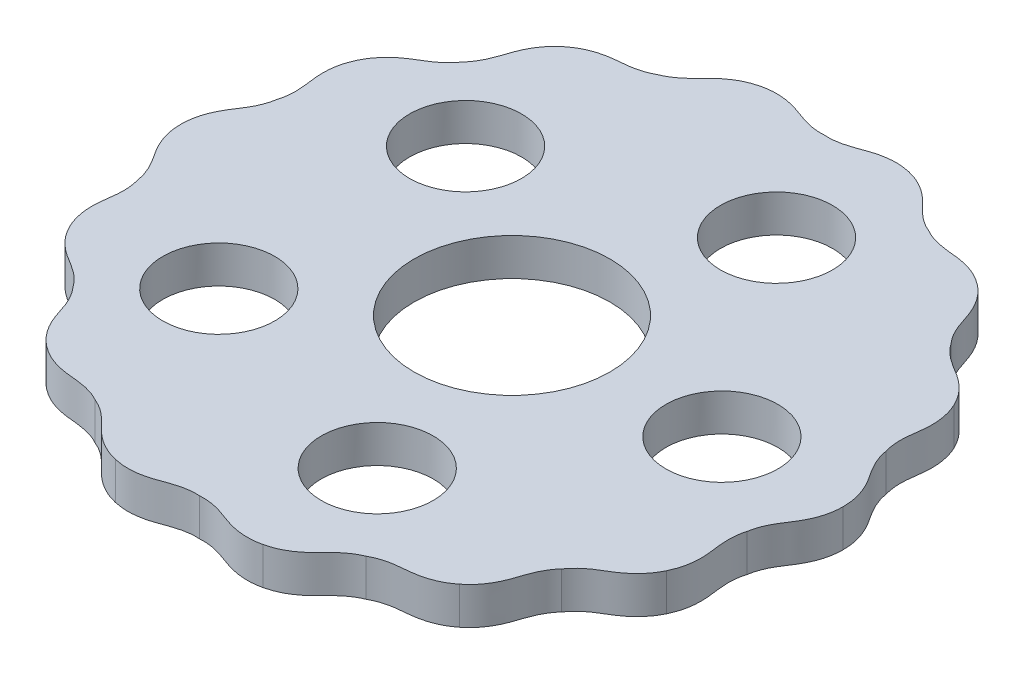
SolidWorks part; units mm, degrees
ref_plane "Front Plane" through (0, 0, 0) normal (0, 0, 1) x (1, 0, 0)
ref_plane "Top Plane" through (0, 0, 0) normal (0, 1, 0) x (1, 0, 0)
ref_plane "Right Plane" through (0, 0, 0) normal (1, 0, 0) x (0, 0, -1)
sketch "Sketch1" plane through (0, 0, 0) normal (0, 1, 0) x (1, 0, 0)
  line L0 (0, 0) -> (37.5, 0) construction
  line L1 (0, 0) -> (37.4807, 1.2019) construction
  line L2 (0, 0) -> (37.423, 2.4026) construction
  line L3 (0, 0) -> (37.3267, 3.6009) construction
  line L4 (0, 0) -> (37.1921, 4.7954) construction
  line L5 (0, 0) -> (37.0193, 5.985) construction
  line L6 (0, 0) -> (36.8085, 7.1684) construction
  line L7 (0, 0) -> (36.5598, 8.3445) construction
  line L8 (0, 0) -> (36.2736, 9.512) construction
  line L9 (0, 0) -> (35.95, 10.6698) construction
  line L10 (0, 0) -> (35.5896, 11.8166) construction
  line L11 (0, 0) -> (35.1926, 12.9512) construction
  line L12 (0, 0) -> (34.7594, 14.0725) construction
  line L13 (0, 0) -> (34.2905, 15.1794) construction
  line L14 (0, 0) -> (33.7863, 16.2706) construction
  line L15 (37.5, 0) -> (38.5, 0) construction
  line L16 (37.4807, 1.2019) -> (38.3521, 1.6927) construction
  line L17 (37.423, 2.4026) -> (37.9413, 3.2578) construction
  line L18 (37.3267, 3.6009) -> (37.3588, 4.6003) construction
  line L19 (37.1921, 4.7954) -> (36.7296, 5.682) construction
  line L20 (37.0193, 5.985) -> (36.1812, 6.5305) construction
  line L21 (36.8085, 7.1684) -> (35.8105, 7.2325) construction
  line L22 (36.5598, 8.3445) -> (35.5849, 8.122) construction
  line L23 (37, 0.0019) -> (37, 0)
  line L24 (33.3367, 16.052) -> (33.3358, 16.0537)
  line L25 (37, -0.0019) -> (37, 0)
  line L26 (33.3367, -16.052) -> (33.3358, -16.0537)
  line L27 (33.335, -16.0554) -> (33.3358, -16.0537)
  line L28 (23.0706, -28.9266) -> (23.0691, -28.9278)
  line L29 (23.0677, -28.9289) -> (23.0691, -28.9278)
  line L30 (8.2351, -36.0719) -> (8.2333, -36.0723)
  line L31 (8.2315, -36.0727) -> (8.2333, -36.0723)
  line L32 (-8.2315, -36.0727) -> (-8.2333, -36.0723)
  line L33 (-8.2351, -36.0719) -> (-8.2333, -36.0723)
  line L34 (-23.0677, -28.9289) -> (-23.0691, -28.9278)
  line L35 (-23.0706, -28.9266) -> (-23.0691, -28.9278)
  line L36 (-33.335, -16.0554) -> (-33.3358, -16.0537)
  line L37 (-33.3367, -16.052) -> (-33.3358, -16.0537)
  line L38 (-37, -0.0019) -> (-37, 0)
  line L39 (-37, 0.0019) -> (-37, 0)
  line L40 (-33.3367, 16.052) -> (-33.3358, 16.0537)
  line L41 (-33.335, 16.0554) -> (-33.3358, 16.0537)
  line L42 (-23.0706, 28.9266) -> (-23.0691, 28.9278)
  line L43 (-23.0677, 28.9289) -> (-23.0691, 28.9278)
  line L44 (-8.2351, 36.0719) -> (-8.2333, 36.0723)
  line L45 (-8.2315, 36.0727) -> (-8.2333, 36.0723)
  line L46 (8.2315, 36.0727) -> (8.2333, 36.0723)
  line L47 (8.2351, 36.0719) -> (8.2333, 36.0723)
  line L48 (23.0677, 28.9289) -> (23.0691, 28.9278)
  line L49 (23.0706, 28.9266) -> (23.0691, 28.9278)
  line L50 (33.335, 16.0554) -> (33.3358, 16.0537)
  line L51 (35.5, 0.0037) -> (35.5, 0)
  line L52 (31.986, 15.3995) -> (31.9844, 15.4029)
  line L53 (35.5, -0.0037) -> (35.5, 0)
  line L54 (31.986, -15.3995) -> (31.9844, -15.4029)
  line L55 (31.9828, -15.4062) -> (31.9844, -15.4029)
  line L56 (22.1368, -27.7527) -> (22.1339, -27.755)
  line L57 (22.131, -27.7573) -> (22.1339, -27.755)
  line L58 (7.9031, -34.6091) -> (7.8995, -34.6099)
  line L59 (7.8959, -34.6108) -> (7.8995, -34.6099)
  line L60 (-7.8959, -34.6108) -> (-7.8995, -34.6099)
  line L61 (-7.9031, -34.6091) -> (-7.8995, -34.6099)
  line L62 (-22.131, -27.7573) -> (-22.1339, -27.755)
  line L63 (-22.1368, -27.7527) -> (-22.1339, -27.755)
  line L64 (-31.9828, -15.4062) -> (-31.9844, -15.4029)
  line L65 (-31.986, -15.3995) -> (-31.9844, -15.4029)
  line L66 (-35.5, -0.0037) -> (-35.5, 0)
  line L67 (-35.5, 0.0037) -> (-35.5, 0)
  line L68 (-31.986, 15.3995) -> (-31.9844, 15.4029)
  line L69 (-31.9828, 15.4062) -> (-31.9844, 15.4029)
  line L70 (-22.1368, 27.7527) -> (-22.1339, 27.755)
  line L71 (-22.131, 27.7573) -> (-22.1339, 27.755)
  line L72 (-7.9031, 34.6091) -> (-7.8995, 34.6099)
  line L73 (-7.8959, 34.6108) -> (-7.8995, 34.6099)
  line L74 (7.8959, 34.6108) -> (7.8995, 34.6099)
  line L75 (7.9031, 34.6091) -> (7.8995, 34.6099)
  line L76 (22.131, 27.7573) -> (22.1339, 27.755)
  line L77 (22.1368, 27.7527) -> (22.1339, 27.755)
  line L78 (31.9828, 15.4062) -> (31.9844, 15.4029)
  circle A0 centre (0, 0) radius 35 construction
  circle A1 centre (37.5, 0) radius 2.5 construction
  circle A2 centre (0, 0) radius 37.5 construction
  spline S0 degree 3 poles (35.5849, 8.122) (35.6266, 7.5364) (36.0345, 6.7125) (36.7836, 5.6218) (37.4152, 4.5501) (38.2239, 2.702) (38.5014, 1.1074) (38.5, 0) knots 0 0 0 0 0.195516 0.310928 0.453873 0.621058 1 1 1 1
  spline S1 degree 3 poles (35.5849, 8.122) (35.3683, 8.6678) (35.3784, 9.5871) (35.5801, 10.8948) (35.6841, 12.1344) (35.611, 14.1503) (35.169, 15.7074) (34.6873, 16.7045) knots 0 0 0 0 0.195516 0.310928 0.453873 0.621058 1 1 1 1
  spline S2 degree 1 poles (34.1119, 7.7858) (33.3367, 16.052) knots 0 0 1 1 construction
  spline S3 degree 1 poles (34.1119, 7.7858) (37, 0.0019) knots 0 0 1 1 construction
  spline S4 degree 3 poles (33.3367, 16.052) (33.6005, 15.5058) (33.9037, 14.6401) (34.1146, 13.4372) (34.174, 12.5211) (34.1413, 11.5771) (34.0239, 10.6392) (33.8823, 9.6155) (33.9055, 8.625) (34.0243, 8.0514) (34.1119, 7.7858) knots 0.015853 0.015853 0.015853 0.015853 0.26189 0.384908 0.507927 0.630945 0.753963 0.876982 0.938491 1 1 1 1
  spline S5 degree 3 poles (34.1119, 7.7858) (34.1483, 7.5085) (34.2901, 6.9402) (34.6989, 6.0377) (35.2706, 5.1769) (35.7834, 4.3828) (36.2224, 3.5464) (36.5664, 2.6953) (36.8983, 1.52) (37.0008, 0.6085) (37, 0.0019) knots 0.015853 0.015853 0.015853 0.015853 0.077362 0.138872 0.26189 0.384908 0.507927 0.630945 0.753963 1 1 1 1
  spline S6 degree 3 poles (37, -0.0019) (37.0008, -0.6085) (36.8983, -1.52) (36.5664, -2.6953) (36.2224, -3.5464) (35.7834, -4.3828) (35.2706, -5.1769) (34.6989, -6.0377) (34.2901, -6.9402) (34.1483, -7.5085) (34.1119, -7.7858) knots 0.015853 0.015853 0.015853 0.015853 0.26189 0.384908 0.507927 0.630945 0.753963 0.876982 0.938491 1 1 1 1
  spline S7 degree 3 poles (34.1119, -7.7858) (34.0243, -8.0514) (33.9055, -8.625) (33.8823, -9.6155) (34.0239, -10.6392) (34.1413, -11.5771) (34.174, -12.5211) (34.1146, -13.4372) (33.9037, -14.6401) (33.6005, -15.5058) (33.3367, -16.052) knots 0.015853 0.015853 0.015853 0.015853 0.077362 0.138872 0.26189 0.384908 0.507927 0.630945 0.753963 1 1 1 1
  spline S8 degree 3 poles (33.335, -16.0554) (33.0725, -16.6022) (32.5847, -17.3791) (31.7758, -18.2939) (31.0965, -18.9115) (30.3381, -19.4746) (29.5316, -19.9675) (28.6429, -20.4951) (27.8831, -21.1308) (27.5087, -21.5813) (27.3556, -21.8154) knots 0.015853 0.015853 0.015853 0.015853 0.26189 0.384908 0.507927 0.630945 0.753963 0.876982 0.938491 1 1 1 1
  spline S9 degree 3 poles (27.3556, -21.8154) (27.1615, -22.0167) (26.8056, -22.4819) (26.3549, -23.3642) (26.0383, -24.348) (25.7371, -25.2439) (25.357, -26.1087) (24.906, -26.9083) (24.1941, -27.9005) (23.5453, -28.549) (23.0706, -28.9266) knots 0.015853 0.015853 0.015853 0.015853 0.077362 0.138872 0.26189 0.384908 0.507927 0.630945 0.753963 1 1 1 1
  spline S10 degree 3 poles (23.0677, -28.9289) (22.5939, -29.3077) (21.8173, -29.796) (20.6915, -30.2693) (19.8116, -30.531) (18.884, -30.7092) (17.9435, -30.8034) (16.9139, -30.8931) (15.9535, -31.1362) (15.4207, -31.3797) (15.1812, -31.5241) knots 0.015853 0.015853 0.015853 0.015853 0.26189 0.384908 0.507927 0.630945 0.753963 0.876982 0.938491 1 1 1 1
  spline S11 degree 3 poles (15.1812, -31.5241) (14.919, -31.6213) (14.3964, -31.886) (13.6076, -32.4854) (12.8955, -33.2344) (12.2354, -33.9109) (11.5177, -34.5251) (10.7645, -35.0499) (9.6926, -35.6349) (8.8266, -35.9377) (8.2351, -36.0719) knots 0.015853 0.015853 0.015853 0.015853 0.077362 0.138872 0.26189 0.384908 0.507927 0.630945 0.753963 1 1 1 1
  spline S12 degree 3 poles (8.2315, -36.0727) (7.6402, -36.2085) (6.7287, -36.3114) (5.5091, -36.2494) (4.6028, -36.1034) (3.6897, -35.8614) (2.8014, -35.5383) (1.8349, -35.1724) (0.8641, -34.9747) (0.2785, -34.9629) (0, -34.9891) knots 0.015853 0.015853 0.015853 0.015853 0.26189 0.384908 0.507927 0.630945 0.753963 0.876982 0.938491 1 1 1 1
  spline S13 degree 3 poles (0, -34.9891) (-0.2785, -34.9629) (-0.8641, -34.9747) (-1.8349, -35.1724) (-2.8014, -35.5383) (-3.6897, -35.8614) (-4.6028, -36.1034) (-5.5091, -36.2494) (-6.7287, -36.3114) (-7.6402, -36.2085) (-8.2315, -36.0727) knots 0.015853 0.015853 0.015853 0.015853 0.077362 0.138872 0.26189 0.384908 0.507927 0.630945 0.753963 1 1 1 1
  spline S14 degree 3 poles (-8.2351, -36.0719) (-8.8266, -35.9377) (-9.6926, -35.6349) (-10.7645, -35.0499) (-11.5177, -34.5251) (-12.2354, -33.9109) (-12.8955, -33.2344) (-13.6076, -32.4854) (-14.3964, -31.886) (-14.919, -31.6213) (-15.1812, -31.5241) knots 0.015853 0.015853 0.015853 0.015853 0.26189 0.384908 0.507927 0.630945 0.753963 0.876982 0.938491 1 1 1 1
  spline S15 degree 3 poles (-15.1812, -31.5241) (-15.4207, -31.3797) (-15.9535, -31.1362) (-16.9139, -30.8931) (-17.9435, -30.8034) (-18.884, -30.7092) (-19.8116, -30.531) (-20.6915, -30.2693) (-21.8173, -29.796) (-22.5939, -29.3077) (-23.0677, -28.9289) knots 0.015853 0.015853 0.015853 0.015853 0.077362 0.138872 0.26189 0.384908 0.507927 0.630945 0.753963 1 1 1 1
  spline S16 degree 3 poles (-23.0706, -28.9266) (-23.5453, -28.549) (-24.1941, -27.9005) (-24.906, -26.9083) (-25.357, -26.1087) (-25.7371, -25.2439) (-26.0383, -24.348) (-26.3549, -23.3642) (-26.8056, -22.4819) (-27.1615, -22.0167) (-27.3556, -21.8154) knots 0.015853 0.015853 0.015853 0.015853 0.26189 0.384908 0.507927 0.630945 0.753963 0.876982 0.938491 1 1 1 1
  spline S17 degree 3 poles (-27.3556, -21.8154) (-27.5087, -21.5813) (-27.8831, -21.1308) (-28.6429, -20.4951) (-29.5316, -19.9675) (-30.3381, -19.4746) (-31.0965, -18.9115) (-31.7758, -18.2939) (-32.5847, -17.3791) (-33.0725, -16.6022) (-33.335, -16.0554) knots 0.015853 0.015853 0.015853 0.015853 0.077362 0.138872 0.26189 0.384908 0.507927 0.630945 0.753963 1 1 1 1
  spline S18 degree 3 poles (-33.3367, -16.052) (-33.6005, -15.5058) (-33.9037, -14.6401) (-34.1146, -13.4372) (-34.174, -12.5211) (-34.1413, -11.5771) (-34.0239, -10.6392) (-33.8823, -9.6155) (-33.9055, -8.625) (-34.0243, -8.0514) (-34.1119, -7.7858) knots 0.015853 0.015853 0.015853 0.015853 0.26189 0.384908 0.507927 0.630945 0.753963 0.876982 0.938491 1 1 1 1
  spline S19 degree 3 poles (-34.1119, -7.7858) (-34.1483, -7.5085) (-34.2901, -6.9402) (-34.6989, -6.0377) (-35.2706, -5.1769) (-35.7834, -4.3828) (-36.2224, -3.5464) (-36.5664, -2.6953) (-36.8983, -1.52) (-37.0008, -0.6085) (-37, -0.0019) knots 0.015853 0.015853 0.015853 0.015853 0.077362 0.138872 0.26189 0.384908 0.507927 0.630945 0.753963 1 1 1 1
  spline S20 degree 3 poles (-37, 0.0019) (-37.0008, 0.6085) (-36.8983, 1.52) (-36.5664, 2.6953) (-36.2224, 3.5464) (-35.7834, 4.3828) (-35.2706, 5.1769) (-34.6989, 6.0377) (-34.2901, 6.9402) (-34.1483, 7.5085) (-34.1119, 7.7858) knots 0.015853 0.015853 0.015853 0.015853 0.26189 0.384908 0.507927 0.630945 0.753963 0.876982 0.938491 1 1 1 1
  spline S21 degree 3 poles (-34.1119, 7.7858) (-34.0243, 8.0514) (-33.9055, 8.625) (-33.8823, 9.6155) (-34.0239, 10.6392) (-34.1413, 11.5771) (-34.174, 12.5211) (-34.1146, 13.4372) (-33.9037, 14.6401) (-33.6005, 15.5058) (-33.3367, 16.052) knots 0.015853 0.015853 0.015853 0.015853 0.077362 0.138872 0.26189 0.384908 0.507927 0.630945 0.753963 1 1 1 1
  spline S22 degree 3 poles (-33.335, 16.0554) (-33.0725, 16.6022) (-32.5847, 17.3791) (-31.7758, 18.2939) (-31.0965, 18.9115) (-30.3381, 19.4746) (-29.5316, 19.9675) (-28.6429, 20.4951) (-27.8831, 21.1308) (-27.5087, 21.5813) (-27.3556, 21.8154) knots 0.015853 0.015853 0.015853 0.015853 0.26189 0.384908 0.507927 0.630945 0.753963 0.876982 0.938491 1 1 1 1
  spline S23 degree 3 poles (-27.3556, 21.8154) (-27.1615, 22.0167) (-26.8056, 22.4819) (-26.3549, 23.3642) (-26.0383, 24.348) (-25.7371, 25.2439) (-25.357, 26.1087) (-24.906, 26.9083) (-24.1941, 27.9005) (-23.5453, 28.549) (-23.0706, 28.9266) knots 0.015853 0.015853 0.015853 0.015853 0.077362 0.138872 0.26189 0.384908 0.507927 0.630945 0.753963 1 1 1 1
  spline S24 degree 3 poles (-23.0677, 28.9289) (-22.5939, 29.3077) (-21.8173, 29.796) (-20.6915, 30.2693) (-19.8116, 30.531) (-18.884, 30.7092) (-17.9435, 30.8034) (-16.9139, 30.8931) (-15.9535, 31.1362) (-15.4207, 31.3797) (-15.1812, 31.5241) knots 0.015853 0.015853 0.015853 0.015853 0.26189 0.384908 0.507927 0.630945 0.753963 0.876982 0.938491 1 1 1 1
  spline S25 degree 3 poles (-15.1812, 31.5241) (-14.919, 31.6213) (-14.3964, 31.886) (-13.6076, 32.4854) (-12.8955, 33.2344) (-12.2354, 33.9109) (-11.5177, 34.5251) (-10.7645, 35.0499) (-9.6926, 35.6349) (-8.8266, 35.9377) (-8.2351, 36.0719) knots 0.015853 0.015853 0.015853 0.015853 0.077362 0.138872 0.26189 0.384908 0.507927 0.630945 0.753963 1 1 1 1
  spline S26 degree 3 poles (-8.2315, 36.0727) (-7.6402, 36.2085) (-6.7287, 36.3114) (-5.5091, 36.2494) (-4.6028, 36.1034) (-3.6897, 35.8614) (-2.8014, 35.5383) (-1.8349, 35.1724) (-0.8641, 34.9747) (-0.2785, 34.9629) (0, 34.9891) knots 0.015853 0.015853 0.015853 0.015853 0.26189 0.384908 0.507927 0.630945 0.753963 0.876982 0.938491 1 1 1 1
  spline S27 degree 3 poles (0, 34.9891) (0.2785, 34.9629) (0.8641, 34.9747) (1.8349, 35.1724) (2.8014, 35.5383) (3.6897, 35.8614) (4.6028, 36.1034) (5.5091, 36.2494) (6.7287, 36.3114) (7.6402, 36.2085) (8.2315, 36.0727) knots 0.015853 0.015853 0.015853 0.015853 0.077362 0.138872 0.26189 0.384908 0.507927 0.630945 0.753963 1 1 1 1
  spline S28 degree 3 poles (8.2351, 36.0719) (8.8266, 35.9377) (9.6926, 35.6349) (10.7645, 35.0499) (11.5177, 34.5251) (12.2354, 33.9109) (12.8955, 33.2344) (13.6076, 32.4854) (14.3964, 31.886) (14.919, 31.6213) (15.1812, 31.5241) knots 0.015853 0.015853 0.015853 0.015853 0.26189 0.384908 0.507927 0.630945 0.753963 0.876982 0.938491 1 1 1 1
  spline S29 degree 3 poles (15.1812, 31.5241) (15.4207, 31.3797) (15.9535, 31.1362) (16.9139, 30.8931) (17.9435, 30.8034) (18.884, 30.7092) (19.8116, 30.531) (20.6915, 30.2693) (21.8173, 29.796) (22.5939, 29.3077) (23.0677, 28.9289) knots 0.015853 0.015853 0.015853 0.015853 0.077362 0.138872 0.26189 0.384908 0.507927 0.630945 0.753963 1 1 1 1
  spline S30 degree 3 poles (23.0706, 28.9266) (23.5453, 28.549) (24.1941, 27.9005) (24.906, 26.9083) (25.357, 26.1087) (25.7371, 25.2439) (26.0383, 24.348) (26.3549, 23.3642) (26.8056, 22.4819) (27.1615, 22.0167) (27.3556, 21.8154) knots 0.015853 0.015853 0.015853 0.015853 0.26189 0.384908 0.507927 0.630945 0.753963 0.876982 0.938491 1 1 1 1
  spline S31 degree 3 poles (27.3556, 21.8154) (27.5087, 21.5813) (27.8831, 21.1308) (28.6429, 20.4951) (29.5316, 19.9675) (30.3381, 19.4746) (31.0965, 18.9115) (31.7758, 18.2939) (32.5847, 17.3791) (33.0725, 16.6022) (33.335, 16.0554) knots 0.015853 0.015853 0.015853 0.015853 0.077362 0.138872 0.26189 0.384908 0.507927 0.630945 0.753963 1 1 1 1
  spline S32 degree 1 poles (32.6448, 7.451) (35.5, 0.0037) knots 0 0 1 1 construction
  spline S33 degree 1 poles (32.6448, 7.451) (31.986, 15.3995) knots 0 0 1 1 construction
  spline S34 degree 3 poles (35.5, 0.0037) (35.5006, 0.4959) (35.4183, 1.2336) (35.1496, 2.1927) (34.8707, 2.8896) (34.4997, 3.6015) (34.1394, 4.1652) (33.6939, 4.8394) (33.3068, 5.4873) (32.9751, 6.1975) (32.758, 6.8733) (32.6748, 7.2607) (32.6448, 7.451) knots 0.023011 0.023011 0.023011 0.023011 0.267258 0.389382 0.511505 0.633629 0.755753 0.816814 0.877876 0.938938 0.969469 1 1 1 1
  spline S35 degree 3 poles (32.6448, 7.451) (32.5893, 7.6354) (32.4961, 8.0206) (32.3985, 8.7236) (32.3893, 9.5074) (32.4569, 10.2591) (32.5657, 11.0598) (32.6458, 11.724) (32.6712, 12.5264) (32.6201, 13.2752) (32.446, 14.256) (32.2001, 14.9563) (31.986, 15.3995) knots 0.023011 0.023011 0.023011 0.023011 0.053542 0.084072 0.145134 0.206196 0.267258 0.389382 0.511505 0.633629 0.755753 1 1 1 1
  spline S36 degree 3 poles (32.6448, -7.451) (32.6748, -7.2607) (32.758, -6.8733) (32.9751, -6.1975) (33.3068, -5.4873) (33.6939, -4.8394) (34.1394, -4.1652) (34.4997, -3.6015) (34.8707, -2.8896) (35.1496, -2.1927) (35.4183, -1.2336) (35.5006, -0.4959) (35.5, -0.0037) knots 0.023011 0.023011 0.023011 0.023011 0.053542 0.084072 0.145134 0.206196 0.267258 0.389382 0.511505 0.633629 0.755753 1 1 1 1
  spline S37 degree 3 poles (31.986, -15.3995) (32.2001, -14.9563) (32.446, -14.256) (32.6201, -13.2752) (32.6712, -12.5264) (32.6458, -11.724) (32.5657, -11.0598) (32.4569, -10.2591) (32.3893, -9.5074) (32.3985, -8.7236) (32.4961, -8.0206) (32.5893, -7.6354) (32.6448, -7.451) knots 0.023011 0.023011 0.023011 0.023011 0.267258 0.389382 0.511505 0.633629 0.755753 0.816814 0.877876 0.938938 0.969469 1 1 1 1
  spline S38 degree 3 poles (26.1791, -20.8771) (26.2887, -20.7187) (26.5317, -20.4057) (27.0205, -19.8911) (27.6275, -19.3952) (28.2574, -18.9793) (28.9513, -18.5652) (29.5206, -18.2137) (30.1637, -17.7333) (30.7173, -17.2264) (31.3755, -16.4789) (31.7698, -15.8499) (31.9828, -15.4062) knots 0.023011 0.023011 0.023011 0.023011 0.053542 0.084072 0.145134 0.206196 0.267258 0.389382 0.511505 0.633629 0.755753 1 1 1 1
  spline S39 degree 3 poles (22.1368, -27.7527) (22.522, -27.4463) (23.0474, -26.922) (23.6297, -26.1139) (24.0007, -25.4614) (24.326, -24.7275) (24.542, -24.0943) (24.7914, -23.3257) (25.0566, -22.619) (25.405, -21.9169) (25.798, -21.3258) (26.0491, -21.0192) (26.1791, -20.8771) knots 0.023011 0.023011 0.023011 0.023011 0.267258 0.389382 0.511505 0.633629 0.755753 0.816814 0.877876 0.938938 0.969469 1 1 1 1
  spline S40 degree 3 poles (14.5283, -30.1683) (14.6957, -30.0732) (15.0505, -29.8966) (15.7143, -29.645) (16.4763, -29.4616) (17.2242, -29.3602) (18.0291, -29.2882) (18.6945, -29.2185) (19.4823, -29.0647) (20.201, -28.8482) (21.1184, -28.4603) (21.7465, -28.0647) (22.131, -27.7573) knots 0.023011 0.023011 0.023011 0.023011 0.053542 0.084072 0.145134 0.206196 0.267258 0.389382 0.511505 0.633629 0.755753 1 1 1 1
  spline S41 degree 3 poles (7.9031, -34.6091) (8.3831, -34.5002) (9.084, -34.2557) (9.9593, -33.7804) (10.5766, -33.3534) (11.1881, -32.8334) (11.6575, -32.3566) (12.2156, -31.7723) (12.7612, -31.2507) (13.3797, -30.7693) (13.9903, -30.4072) (14.3495, -30.2399) (14.5283, -30.1683) knots 0.023011 0.023011 0.023011 0.023011 0.267258 0.389382 0.511505 0.633629 0.755753 0.816814 0.877876 0.938938 0.969469 1 1 1 1
  spline S42 degree 3 poles (0, -33.4843) (0.1922, -33.4712) (0.5884, -33.4661) (1.2956, -33.5274) (2.0617, -33.6928) (2.7796, -33.926) (3.536, -34.2103) (4.1657, -34.4362) (4.9423, -34.6394) (5.6838, -34.7562) (6.6786, -34.8048) (7.4161, -34.7209) (7.8959, -34.6108) knots 0.023011 0.023011 0.023011 0.023011 0.053542 0.084072 0.145134 0.206196 0.267258 0.389382 0.511505 0.633629 0.755753 1 1 1 1
  spline S43 degree 3 poles (-7.8959, -34.6108) (-7.4161, -34.7209) (-6.6786, -34.8048) (-5.6838, -34.7562) (-4.9423, -34.6394) (-4.1657, -34.4362) (-3.536, -34.2103) (-2.7796, -33.926) (-2.0617, -33.6928) (-1.2956, -33.5274) (-0.5884, -33.4661) (-0.1922, -33.4712) (0, -33.4843) knots 0.023011 0.023011 0.023011 0.023011 0.267258 0.389382 0.511505 0.633629 0.755753 0.816814 0.877876 0.938938 0.969469 1 1 1 1
  spline S44 degree 3 poles (-14.5283, -30.1683) (-14.3495, -30.2399) (-13.9903, -30.4072) (-13.3797, -30.7693) (-12.7612, -31.2507) (-12.2156, -31.7723) (-11.6575, -32.3566) (-11.1881, -32.8334) (-10.5766, -33.3534) (-9.9593, -33.7804) (-9.084, -34.2557) (-8.3831, -34.5002) (-7.9031, -34.6091) knots 0.023011 0.023011 0.023011 0.023011 0.053542 0.084072 0.145134 0.206196 0.267258 0.389382 0.511505 0.633629 0.755753 1 1 1 1
  spline S45 degree 3 poles (-22.131, -27.7573) (-21.7465, -28.0647) (-21.1184, -28.4603) (-20.201, -28.8482) (-19.4823, -29.0647) (-18.6945, -29.2185) (-18.0291, -29.2882) (-17.2242, -29.3602) (-16.4763, -29.4616) (-15.7143, -29.645) (-15.0505, -29.8966) (-14.6957, -30.0732) (-14.5283, -30.1683) knots 0.023011 0.023011 0.023011 0.023011 0.267258 0.389382 0.511505 0.633629 0.755753 0.816814 0.877876 0.938938 0.969469 1 1 1 1
  spline S46 degree 3 poles (-26.1791, -20.8771) (-26.0491, -21.0192) (-25.798, -21.3258) (-25.405, -21.9169) (-25.0566, -22.619) (-24.7914, -23.3257) (-24.542, -24.0943) (-24.326, -24.7275) (-24.0007, -25.4614) (-23.6297, -26.1139) (-23.0474, -26.922) (-22.522, -27.4463) (-22.1368, -27.7527) knots 0.023011 0.023011 0.023011 0.023011 0.053542 0.084072 0.145134 0.206196 0.267258 0.389382 0.511505 0.633629 0.755753 1 1 1 1
  spline S47 degree 3 poles (-31.9828, -15.4062) (-31.7698, -15.8499) (-31.3755, -16.4789) (-30.7173, -17.2264) (-30.1637, -17.7333) (-29.5206, -18.2137) (-28.9513, -18.5652) (-28.2574, -18.9793) (-27.6275, -19.3952) (-27.0205, -19.8911) (-26.5317, -20.4057) (-26.2887, -20.7187) (-26.1791, -20.8771) knots 0.023011 0.023011 0.023011 0.023011 0.267258 0.389382 0.511505 0.633629 0.755753 0.816814 0.877876 0.938938 0.969469 1 1 1 1
  spline S48 degree 3 poles (-32.6448, -7.451) (-32.5893, -7.6354) (-32.4961, -8.0206) (-32.3985, -8.7236) (-32.3893, -9.5074) (-32.4569, -10.2591) (-32.5657, -11.0598) (-32.6458, -11.724) (-32.6712, -12.5264) (-32.6201, -13.2752) (-32.446, -14.256) (-32.2001, -14.9563) (-31.986, -15.3995) knots 0.023011 0.023011 0.023011 0.023011 0.053542 0.084072 0.145134 0.206196 0.267258 0.389382 0.511505 0.633629 0.755753 1 1 1 1
  spline S49 degree 3 poles (-35.5, -0.0037) (-35.5006, -0.4959) (-35.4183, -1.2336) (-35.1496, -2.1927) (-34.8707, -2.8896) (-34.4997, -3.6015) (-34.1394, -4.1652) (-33.6939, -4.8394) (-33.3068, -5.4873) (-32.9751, -6.1975) (-32.758, -6.8733) (-32.6748, -7.2607) (-32.6448, -7.451) knots 0.023011 0.023011 0.023011 0.023011 0.267258 0.389382 0.511505 0.633629 0.755753 0.816814 0.877876 0.938938 0.969469 1 1 1 1
  spline S50 degree 3 poles (-32.6448, 7.451) (-32.6748, 7.2607) (-32.758, 6.8733) (-32.9751, 6.1975) (-33.3068, 5.4873) (-33.6939, 4.8394) (-34.1394, 4.1652) (-34.4997, 3.6015) (-34.8707, 2.8896) (-35.1496, 2.1927) (-35.4183, 1.2336) (-35.5006, 0.4959) (-35.5, 0.0037) knots 0.023011 0.023011 0.023011 0.023011 0.053542 0.084072 0.145134 0.206196 0.267258 0.389382 0.511505 0.633629 0.755753 1 1 1 1
  spline S51 degree 3 poles (-31.986, 15.3995) (-32.2001, 14.9563) (-32.446, 14.256) (-32.6201, 13.2752) (-32.6712, 12.5264) (-32.6458, 11.724) (-32.5657, 11.0598) (-32.4569, 10.2591) (-32.3893, 9.5074) (-32.3985, 8.7236) (-32.4961, 8.0206) (-32.5893, 7.6354) (-32.6448, 7.451) knots 0.023011 0.023011 0.023011 0.023011 0.267258 0.389382 0.511505 0.633629 0.755753 0.816814 0.877876 0.938938 0.969469 1 1 1 1
  spline S52 degree 3 poles (-26.1791, 20.8771) (-26.2887, 20.7187) (-26.5317, 20.4057) (-27.0205, 19.8911) (-27.6275, 19.3952) (-28.2574, 18.9793) (-28.9513, 18.5652) (-29.5206, 18.2137) (-30.1637, 17.7333) (-30.7173, 17.2264) (-31.3755, 16.4789) (-31.7698, 15.8499) (-31.9828, 15.4062) knots 0.023011 0.023011 0.023011 0.023011 0.053542 0.084072 0.145134 0.206196 0.267258 0.389382 0.511505 0.633629 0.755753 1 1 1 1
  spline S53 degree 3 poles (-22.1368, 27.7527) (-22.522, 27.4463) (-23.0474, 26.922) (-23.6297, 26.1139) (-24.0007, 25.4614) (-24.326, 24.7275) (-24.542, 24.0943) (-24.7914, 23.3257) (-25.0566, 22.619) (-25.405, 21.9169) (-25.798, 21.3258) (-26.0491, 21.0192) (-26.1791, 20.8771) knots 0.023011 0.023011 0.023011 0.023011 0.267258 0.389382 0.511505 0.633629 0.755753 0.816814 0.877876 0.938938 0.969469 1 1 1 1
  spline S54 degree 3 poles (-14.5283, 30.1683) (-14.6957, 30.0732) (-15.0505, 29.8966) (-15.7143, 29.645) (-16.4763, 29.4616) (-17.2242, 29.3602) (-18.0291, 29.2882) (-18.6945, 29.2185) (-19.4823, 29.0647) (-20.201, 28.8482) (-21.1184, 28.4603) (-21.7465, 28.0647) (-22.131, 27.7573) knots 0.023011 0.023011 0.023011 0.023011 0.053542 0.084072 0.145134 0.206196 0.267258 0.389382 0.511505 0.633629 0.755753 1 1 1 1
  spline S55 degree 3 poles (-7.9031, 34.6091) (-8.3831, 34.5002) (-9.084, 34.2557) (-9.9593, 33.7804) (-10.5766, 33.3534) (-11.1881, 32.8334) (-11.6575, 32.3566) (-12.2156, 31.7723) (-12.7612, 31.2507) (-13.3797, 30.7693) (-13.9903, 30.4072) (-14.3495, 30.2399) (-14.5283, 30.1683) knots 0.023011 0.023011 0.023011 0.023011 0.267258 0.389382 0.511505 0.633629 0.755753 0.816814 0.877876 0.938938 0.969469 1 1 1 1
  spline S56 degree 3 poles (0, 33.4843) (-0.1922, 33.4712) (-0.5884, 33.4661) (-1.2956, 33.5274) (-2.0617, 33.6928) (-2.7796, 33.926) (-3.536, 34.2103) (-4.1657, 34.4362) (-4.9423, 34.6394) (-5.6838, 34.7562) (-6.6786, 34.8048) (-7.4161, 34.7209) (-7.8959, 34.6108) knots 0.023011 0.023011 0.023011 0.023011 0.053542 0.084072 0.145134 0.206196 0.267258 0.389382 0.511505 0.633629 0.755753 1 1 1 1
  spline S57 degree 3 poles (7.8959, 34.6108) (7.4161, 34.7209) (6.6786, 34.8048) (5.6838, 34.7562) (4.9423, 34.6394) (4.1657, 34.4362) (3.536, 34.2103) (2.7796, 33.926) (2.0617, 33.6928) (1.2956, 33.5274) (0.5884, 33.4661) (0.1922, 33.4712) (0, 33.4843) knots 0.023011 0.023011 0.023011 0.023011 0.267258 0.389382 0.511505 0.633629 0.755753 0.816814 0.877876 0.938938 0.969469 1 1 1 1
  spline S58 degree 3 poles (14.5283, 30.1683) (14.3495, 30.2399) (13.9903, 30.4072) (13.3797, 30.7693) (12.7612, 31.2507) (12.2156, 31.7723) (11.6575, 32.3566) (11.1881, 32.8334) (10.5766, 33.3534) (9.9593, 33.7804) (9.084, 34.2557) (8.3831, 34.5002) (7.9031, 34.6091) knots 0.023011 0.023011 0.023011 0.023011 0.053542 0.084072 0.145134 0.206196 0.267258 0.389382 0.511505 0.633629 0.755753 1 1 1 1
  spline S59 degree 3 poles (22.131, 27.7573) (21.7465, 28.0647) (21.1184, 28.4603) (20.201, 28.8482) (19.4823, 29.0647) (18.6945, 29.2185) (18.0291, 29.2882) (17.2242, 29.3602) (16.4763, 29.4616) (15.7143, 29.645) (15.0505, 29.8966) (14.6957, 30.0732) (14.5283, 30.1683) knots 0.023011 0.023011 0.023011 0.023011 0.267258 0.389382 0.511505 0.633629 0.755753 0.816814 0.877876 0.938938 0.969469 1 1 1 1
  spline S60 degree 3 poles (26.1791, 20.8771) (26.0491, 21.0192) (25.798, 21.3258) (25.405, 21.9169) (25.0566, 22.619) (24.7914, 23.3257) (24.542, 24.0943) (24.326, 24.7275) (24.0007, 25.4614) (23.6297, 26.1139) (23.0474, 26.922) (22.522, 27.4463) (22.1368, 27.7527) knots 0.023011 0.023011 0.023011 0.023011 0.053542 0.084072 0.145134 0.206196 0.267258 0.389382 0.511505 0.633629 0.755753 1 1 1 1
  spline S61 degree 3 poles (31.9828, 15.4062) (31.7698, 15.8499) (31.3755, 16.4789) (30.7173, 17.2264) (30.1637, 17.7333) (29.5206, 18.2137) (28.9513, 18.5652) (28.2574, 18.9793) (27.6275, 19.3952) (27.0205, 19.8911) (26.5317, 20.4057) (26.2887, 20.7187) (26.1791, 20.8771) knots 0.023011 0.023011 0.023011 0.023011 0.267258 0.389382 0.511505 0.633629 0.755753 0.816814 0.877876 0.938938 0.969469 1 1 1 1
  point P25 (0, 0)
  point P117 (0, 0)
  point P174 (0, 0)
  dimension "D1" = 70
  dimension "D2" = 5
  dimension "D4" = 25.714
  dimension "D5" = 1
  dimension "D7" = 180
  dimension "D8" = 207.551
  dimension "D6" = 1
  dimension "D9" = 1
  dimension "D10" = 235.102
  dimension "D11" = 1
  dimension "D12" = 1
  dimension "D13" = 1
  dimension "D14" = 1
  dimension "D15" = 1
  dimension "D16" = 262.653
  dimension "D17" = 290.204
  dimension "D18" = 317.755
  dimension "D19" = 345.306
  dimension "D20" = 1.5
  dimension "D22" = 3
  dimension "D3" = 15
  dimension "D21" = 14
  dimension "D23" = 14
extrude "Boss-Extrude3" add sketch "Sketch1" along normal blind 4 contours L51 L53 S36 S37 L54 L55 S38 S39 L56 L57 S40 S41 L58 L59 S42 S43 L60 L61 S44 S45 L62 L63 S46 S47 L64 L65 S48 S49 L66 L67 S50 S51 L68 L69 S52 S53 L70 L71 S54 S55 L72 L73 S56 S57 L74 L75 S58 S59 L76 L77 S60 S61 L78 L52 S35 S34
sketch "Sketch2" plane through (0, 4, 0) normal (0, 1, 0) x (1, 0, 0)
  line L0 (0, 0) -> (22.5, 0)
  line L1 (0, 0) -> (6.9529, -21.3988)
  line L2 (0, 0) -> (-18.2029, -13.2252)
  line L3 (0, 0) -> (-18.2029, 13.2252)
  line L4 (0, 0) -> (6.9529, 21.3988)
  circle A0 centre (0, 0) radius 10.5
  circle A1 centre (22.5, 0) radius 6
  circle A2 centre (6.9529, -21.3988) radius 6
  circle A3 centre (-18.2029, -13.2252) radius 6
  circle A4 centre (-18.2029, 13.2252) radius 6
  circle A5 centre (6.9529, 21.3988) radius 6
  point P16 (0, 0)
  point P21 (0, 0)
  dimension "D1" = 21
  dimension "D3" = 12
  dimension "D2" = 22.5
  dimension "D4" = 5
  dimension "D5" = 5
extrude "Cut-Extrude1" cut sketch "Sketch2" against normal blind 5 contours A4 | A3 | L2 A0 L1 | L3 A0 L2 | L4 A0 L3 | L0 A0 L4 | L1 A0 L0 | A2 | A1 | A5 region at (5.2978, 4, -3.8491) region at (5.2978, 4, 3.8491) region at (-2.0236, 4, 6.2279) region at (-6.5484, 4, 0) region at (-2.0236, 4, -6.2279) region at (22.5, 4, -5.8303) region at (10.3798, 4, 16.682) region at (-12.6579, 4, 11.4235) region at (-23.7478, 4, -15.0268) region at (3.5259, 4, -26.1156)
equation "\"Eccentricity\" = 1mm"
equation "\"Pin Diameter\"= 3mm"
equation "\"D5@Sketch1\"=\"Eccentricity\""
equation "\"D6@Sketch1\"=\"Eccentricity\""
equation "\"D9@Sketch1\"=\"Eccentricity\""
equation "\"D11@Sketch1\"=\"Eccentricity\""
equation "\"D12@Sketch1\"=\"Eccentricity\""
equation "\"D14@Sketch1\"=\"Eccentricity\""
equation "\"D13@Sketch1\"=\"Eccentricity\""
equation "\"D15@Sketch1\"=\"Eccentricity\""
equation "\"Disc Bearing Diameter\"=21"
equation "\"D1@Sketch2\"=\"Disc Bearing Diameter\""
